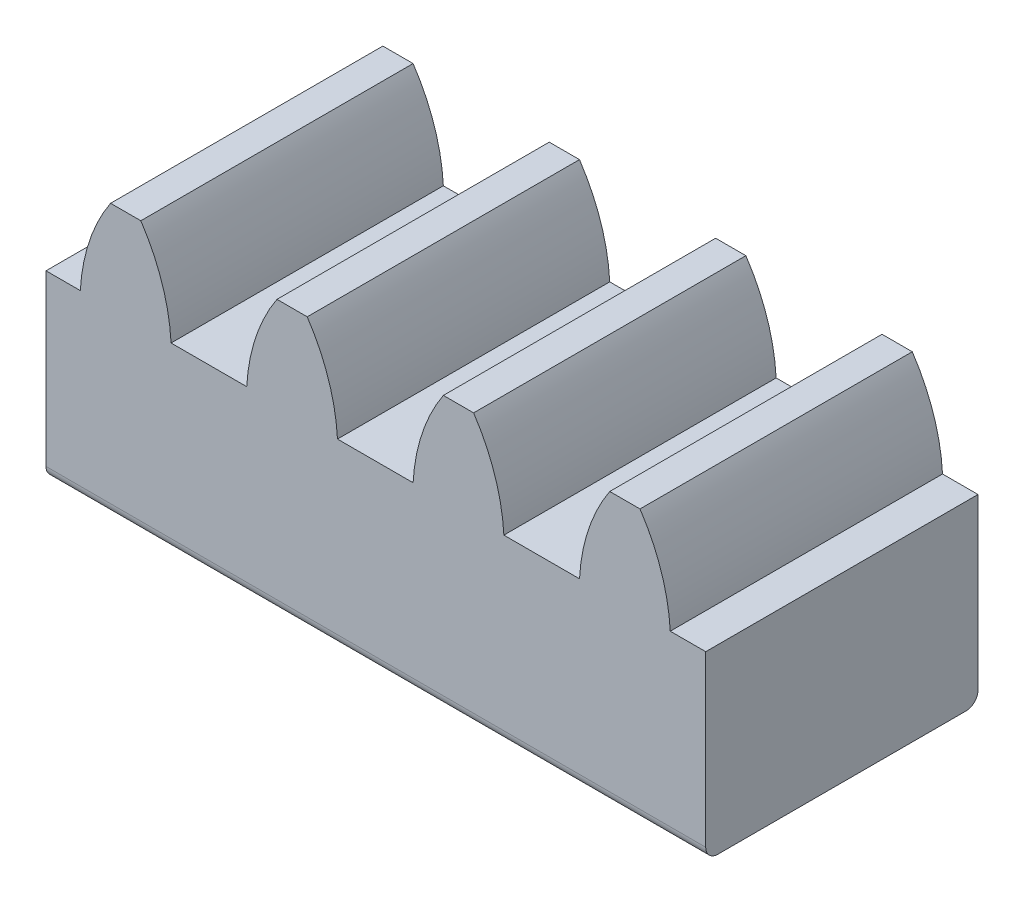
SolidWorks part; units mm, degrees
note: The reader was unsure of these and kept them because the rebuilt part matched: shared geometry of "Sketch1<3>".
ref_plane "Front Plane" through (0, 0, 0) normal (0, 0, 1) x (1, 0, 0)
ref_plane "Top Plane" through (0, 0, 0) normal (0, 1, 0) x (1, 0, 0)
ref_plane "Right Plane" through (0, 0, 0) normal (1, 0, 0) x (0, 0, -1)
sketch "Sketch1" plane through (0, 0, 0) normal (0, 0, 1) x (1, 0, 0)
  line L0 (-55.8407, -27.8293) -> (-55.8407, -33.8096) construction
  line L1 (-60.6927, -40.8293) -> (169.3073, -40.8293)
  line L2 (-60.6927, -40.8293) -> (-60.6927, -34.8293)
  line L3 (-60.6927, -34.8293) -> (169.3073, -34.8293)
  line L4 (169.3073, -40.8293) -> (169.3073, -34.8293)
  line L5 (-56.3407, -31.8293) -> (-55.3407, -31.8293)
  line L6 (12.3073, -36.8293) -> (1.3073, -36.8293) construction
  line L7 (-35.6927, -19.8293) -> (-35.6927, -31.8293) construction
  arc A3 (-57.3407, -34.8293) -> (-56.3407, -31.8293) centre (-51.3498, -35.1596) cw
  arc A5 (-54.3407, -34.8293) -> (-55.3407, -31.8293) centre (-60.3316, -35.1596) ccw
  dimension "D3" = 2
  dimension "D4" = 6
  dimension "D1" = 230
  dimension "D2" = 6
  dimension "D5" = 1
  dimension "D6" = 1
  dimension "D7" = 3
  dimension "D8" = 25
extrude "Boss-Extrude1" add sketch "Sketch1" against normal up to surface (9 mm away) contours L1 L4 L3 L2
extrude "Boss-Extrude2" add sketch "Sketch1<3>" against normal up to surface (9 mm away) up to face at (54.3073, -37.8293, -9)
sketch "Sketch1<3>" plane through (0, 0, 0) normal (0, 0, 1) x (1, 0, 0) same geometry as "Sketch1"
pattern_linear "LPattern1" count 41 spacing 5.5 along (1, 0, 0) of "Boss-Extrude2"
sketch "Sketch2" plane through (0, -40.8293, 0) normal (0, -1, 0) x (1, 0, 0)
  line L0 (-60.6927, -9) -> (-60.6927, 0) construction
  line L1 (-60.6927, -14.5) -> (-75.6927, -14.5)
  line L2 (-60.6927, -14.5) -> (-60.6927, 5.5)
  line L3 (-60.6927, 5.5) -> (-75.6927, 5.5)
  line L4 (-75.6927, -14.5) -> (-75.6927, 5.5)
  line L5 (169.3073, -9) -> (169.3073, 0) construction
  point P8 (169.3073, -4.5)
  point P9 (-60.6927, -4.5)
  dimension "D1" = 15
  dimension "D2" = 20
extrude "Boss-Extrude3" add sketch "Sketch2" against normal blind 5
fillet "Fillet1" radius 10 1 edges at (-60.6927, -35.8293, -4.5)
fillet "Fillet2" radius 3 4 edges at (-60.6927, -38.3293, -14.5) (-75.6927, -38.3293, -14.5) (-75.6927, -38.3293, 5.5) (-60.6927, -38.3293, 5.5)
sketch "Sketch3" plane through (169.3073, 0, 0) normal (1, 0, 0) x (0, 0, -1)
  line L4 (11, -32.8293) -> (-2, -32.8293)
  line L12 (-2, -40.8293) -> (11, -40.8293)
  line L13 (11.5, -40.8293) -> (9, -40.8293) construction
  line L14 (0, -40.8293) -> (-2.5, -40.8293) construction
  line L16 (11, -42.8293) -> (11, -32.8293)
  line L18 (-2, -32.8293) -> (-2, -42.8293)
  line L19 (-2, -42.8293) -> (11, -42.8293)
  line L20 (11, -40.8293) -> (11, -32.8293)
  line L22 (-2, -32.8293) -> (-2, -40.8293)
  line L25 (11, -32.8293) -> (-2, -32.8293)
  dimension "D1" = 2
extrude "Boss-Extrude4" add sketch "Sketch3" along normal blind 5
sketch "Sketch4" plane through (0, 0, 2) normal (0, 0, 1) x (1, 0, 0)
  line L1 (169.3073, -40.8293) -> (172.3073, -40.8293)
  line L2 (169.3073, -40.8293) -> (169.3073, -32.8293)
  line L3 (169.3073, -32.8293) -> (172.3073, -32.8293)
  line L4 (172.3073, -40.8293) -> (172.3073, -32.8293)
  dimension "D1" = 3
  dimension "D2" = 8
extrude "Boss-Extrude5" add sketch "Sketch4" along normal blind 5
fillet "Fillet3" radius 0.4 29 edges at (-74.814, -40.8293, -13.6213) (-75.6927, -40.8293, -4.5) (-74.814, -40.8293, 4.6213) (-68.1927, -40.8293, 5.5) (-61.5713, -40.8293, 4.6213) (-60.6927, -40.8293, 1.25) (54.3073, -40.8293, -9) (54.3073, -40.8293, 0) (172.3073, -40.8293, 4.5) (169.3073, -40.8293, 3.5) (171.8073, -40.8293, -11) (169.3073, -40.8293, -10) (174.3073, -40.8293, -4.5) (-60.6927, -40.8293, -10.25) (-61.5713, -40.8293, -13.6213) (-68.1927, -40.8293, -14.5) (170.8073, -40.8293, 7) (169.3073, -36.8293, 7) (173.3073, -40.8293, 2) (172.3073, -36.8293, 7) (172.3073, -36.8293, 2) (174.3073, -36.8293, -11) (174.3073, -36.8293, 2) (171.8073, -32.8293, -11) (174.3073, -32.8293, -4.5) (173.3073, -32.8293, 2) (172.3073, -32.8293, 4.5) (170.8073, -32.8293, 7) (169.3073, -32.8293, -2)
hole_wizard "Ø3.0mm Dowel Hole1" positions "3DSketch1" profile "Sketch5" hole size "Ø3.0" standard "ANSI Metric"
sketch3d "3DSketch1"
  line L5 (-72.6927, -40.4293, 5.5) -> (-63.6927, -40.4293, 5.5) construction
  point P0 (-65.6927, -40.8293, 1.5)
  point P2 (-65.6927, -40.8293, -10.5)
  point P4 (-71.6927, -40.8293, -4.492)
  dimension "D1" = 10
  dimension "D2" = 4
  dimension "D3" = 4
  dimension "D4" = 10
  dimension "D5" = 10
  dimension "D6" = 4
sketch "Sketch5" plane through (-65.6927, -40.8293, 1.5) normal (1, 0, 0) x (0, 0, -1)
  line L0 (0, 0) -> (0, 7.8112)
  line L1 (0, 7.8112) -> (1.35, 7)
  line L2 (1.35, 7) -> (1.35, 0)
  line L5 (1.35, 0) -> (0, 0)
  line L10 (0, 7.8112) -> (-1.35, 7) construction
  line L11 (0, -6.35) -> (0, 107.95) construction
  dimension "Hole Dia." = 2.7
  dimension "Hole Depth" = 7
  dimension "Drill Angle" = 118
sketch "Sketch7" plane through (0, -35.8293, 0) normal (0, 1, 0) x (1, 0, 0)
  circle A0 centre (-65.6927, -1.5) radius 1.35 construction
  circle A1 centre (-71.6927, 4.492) radius 1.35 construction
  circle A2 centre (-65.6927, 10.5) radius 1.35 construction
  circle A3 centre (-65.6927, -1.5) radius 1.35
  circle A4 centre (-71.6927, 4.492) radius 1.35
  circle A5 centre (-65.6927, 10.5) radius 1.35
sketch "Sketch6" plane through (0, 0, 0) normal (0, 0, 1) x (1, 0, 0)
  line L0 (169.7073, -40.8293) -> (-61.0927, -40.8293) construction
  line L1 (-58.4752, -40.8293) -> (-36.6683, -40.8293)
  line L2 (-58.4752, -40.8293) -> (-58.4752, -24.6511)
  line L3 (-58.4752, -24.6511) -> (-36.6683, -24.6511)
  line L4 (-36.6683, -40.8293) -> (-36.6683, -24.6511)
  line L5 (-58.5752, -40.9293) -> (-58.5752, -24.5511)
  line L6 (-58.5752, -24.5511) -> (-36.5683, -24.5511)
  line L7 (-36.5683, -40.9293) -> (-36.5683, -24.5511)
  line L8 (-58.5752, -40.9293) -> (-36.5683, -40.9293)
  dimension "D1" = 0.1
extrude "Cut-Extrude1" cut sketch "Sketch6" against normal through all
delete or keep bodies "Body-Delete/Keep 1" type delete bodies bodies 108 109
